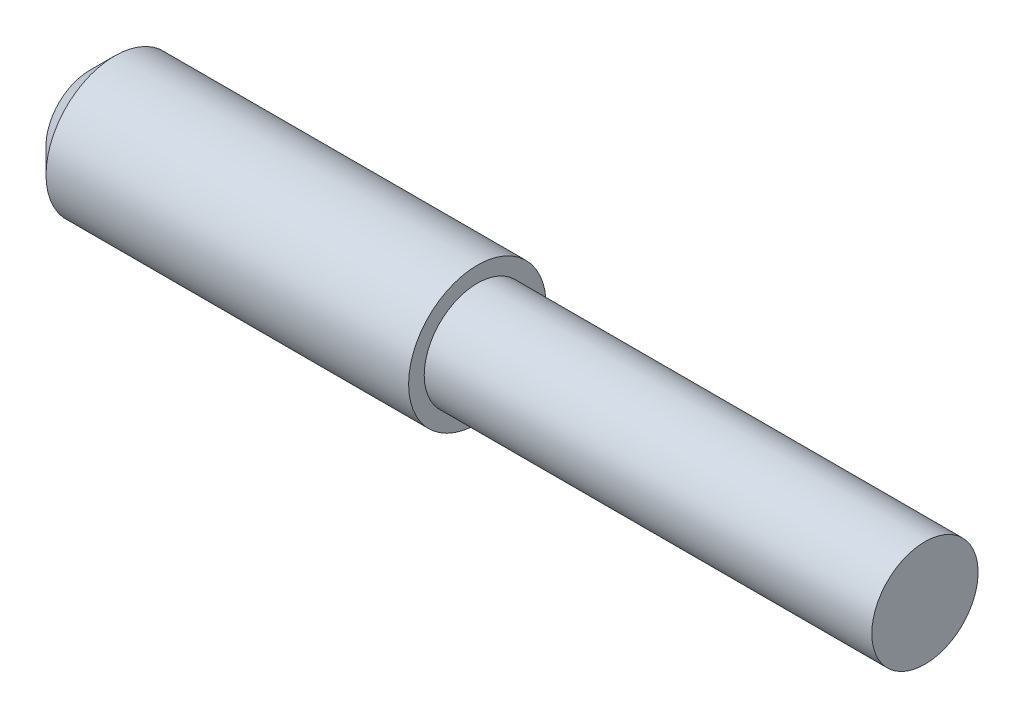
SolidWorks part; units mm, degrees
ref_plane "Front Plane" through (0, 0, 0) normal (0, 0, 1) x (1, 0, 0)
ref_plane "Top Plane" through (0, 0, 0) normal (0, 1, 0) x (1, 0, 0)
ref_plane "Right Plane" through (0, 0, 0) normal (1, 0, 0) x (0, 0, -1)
sketch "Sketch1" plane through (0, 0, 0) normal (0, 0, 1) x (1, 0, 0)
  line L0 (-9.4589, 0) -> (1.0894, 0) construction
  line L1 (0, 2.75) -> (-15.5, 2.75)
  line L2 (-15.5, 2.75) -> (-15.5, 0)
  line L3 (-15.5, 0) -> (17.9, 0)
  line L4 (0, 2.75) -> (0, 2.125)
  line L5 (0, 2.125) -> (0, 0) construction
  line L6 (0, 2.125) -> (17.9, 2.125)
  line L7 (17.9, 2.125) -> (17.9, 0)
  line L8 (5.5, 0) -> (5.5, 2.125) construction
  dimension "D1" = 5.5
  dimension "OD" = 5.5
  dimension "ID" = 4.25
  dimension "D2" = 12.4
  dimension "D3" = 15.5
revolve "Revolve1" add sketch "Sketch1" angle 360 about L0
ref_axis "Axis1" through (0, 0, 0) along (-1, 0, 0)
chamfer "Chamfer1" distance 1 angle 45 1 edges at (-15.5, 0, 2.75)
sketch "Sketch2" [suppressed] plane through (-5.5, 0, 0) normal (-1, 0, 0) x (0, 0, 1)
  circle A0 centre (0, 0) radius 4.75
  circle A1 centre (0, 0) radius 2.75 construction
  circle A2 centre (0, 0) radius 5.75
  dimension "D1" = 2
  dimension "D2" = 1
extrude "Boss-Extrude1" [suppressed] add sketch "Sketch2" against normal blind 30 separate body
sketch "Sketch3" [suppressed] plane through (0, 0, 0) normal (0, 0, 1) x (1, 0, 0)
  line L0 (-5.5, 2.75) -> (-5.5, -2.75) construction
  line L1 (-5.5, -0.8) -> (-4.7, -0.8)
  line L2 (-5.5, -0.8) -> (-5.5, 0.8)
  line L3 (-5.5, 0.8) -> (-4.7, 0.8)
  line L4 (-4.7, -0.8) -> (-4.7, 0.8)
  point P4 (-4.7, 0)
  dimension "D1" = 0.8
  dimension "D2" = 1.6
extrude "Boss-Extrude2" [suppressed] add sketch "Sketch3" along normal up to surface and the other way up to surface
pattern_circular "CirPattern1" [suppressed] count 4 over 360 reverse direction yes of bodies 103
pattern_linear "LPattern1" [suppressed] count 3 spacing 14.8 along (1, 0, 0) of bodies 104
